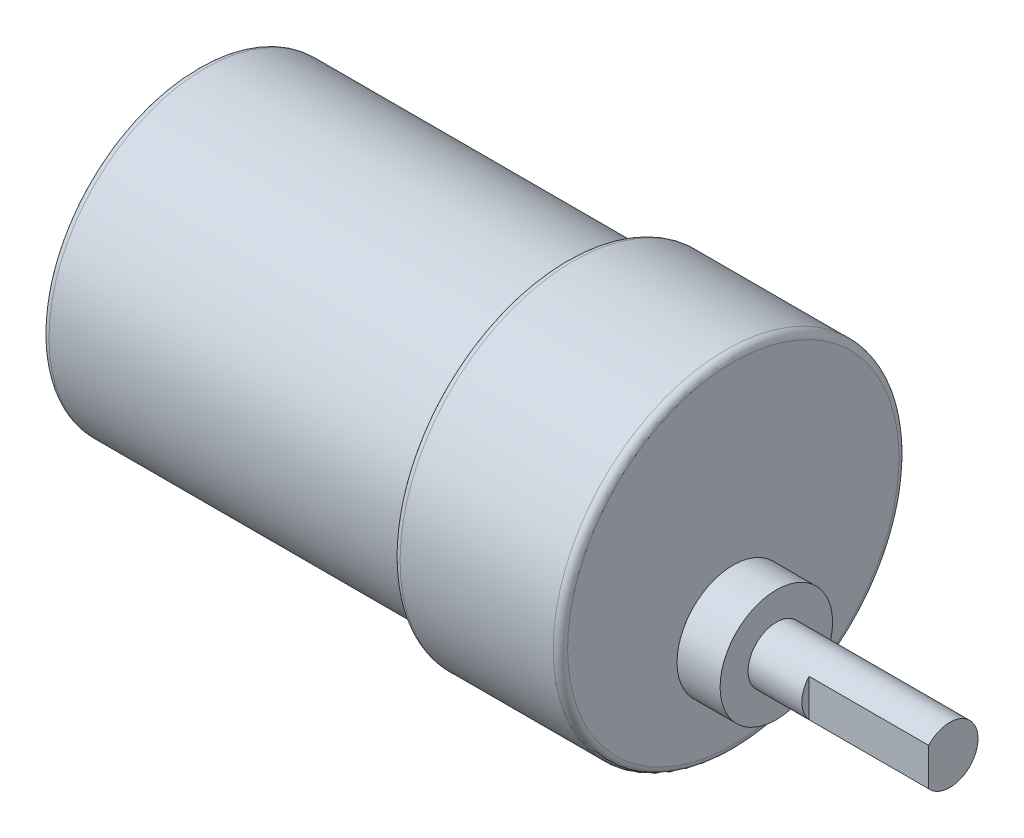
SolidWorks part; units mm, degrees
material "Plain Carbon Steel"
ref_plane "Front Plane" through (0, 0, 0) normal (0, 0, 1) x (1, 0, 0)
ref_plane "Top Plane" through (0, 0, 0) normal (0, 1, 0) x (1, 0, 0)
ref_plane "Right Plane" through (0, 0, 0) normal (1, 0, 0) x (0, 0, -1)
sketch "Sketch1" plane through (0, 0, 0) normal (0, 0, 1) x (1, 0, 0)
  line L0 (0, 3.175) -> (0, 16.51)
  line L1 (0, 16.51) -> (39.116, 16.51)
  line L2 (39.116, 18.3515) -> (56.896, 18.3515)
  line L3 (56.896, 18.3515) -> (56.896, 0)
  line L4 (39.116, 16.51) -> (39.116, 18.3515)
  line L5 (-2.286, 0) -> (56.896, 0) construction
  line L6 (0, 3.175) -> (-2.286, 3.175)
  line L7 (-2.286, 3.175) -> (-2.286, 0)
  line L8 (56.896, 0) -> (-2.286, 0)
  dimension "D1" = 16.51
  dimension "D2" = 39.116
  dimension "D3" = 17.78
  dimension "D4" = 18.3515
  dimension "D5" = 2.286
  dimension "D6" = 3.175
revolve "Revolve1" add sketch "Sketch1" angle 360 about L5
sketch "Sketch2" plane through (56.896, 0, 0) normal (1, 0, 0) x (0, 0, -1)
  line L0 (0, 0) -> (0, -7.0358) construction
  circle A0 centre (0, -7.0358) radius 5.969
  dimension "D2" = 11.938
  dimension "D1" = 7.0358
extrude "Boss-Extrude1" add sketch "Sketch2" along normal blind 4.572
sketch "Sketch3" plane through (61.468, 0, 0) normal (1, 0, 0) x (0, 0, -1)
  circle A0 centre (0, -7.0358) radius 3
  dimension "D1" = 6
extrude "Boss-Extrude2" add sketch "Sketch3" along normal blind 18.415
fillet "Fillet1" radius 0.762 4 edges at (56.896, 0, 18.3515) (39.116, 0, 18.3515) (0, 0, 16.51) (-2.286, 0, 3.175)
sketch "Sketch4" plane through (0, 0, 0) normal (0, 1, 0) x (1, 0, 0)
  line L1 (79.883, -3) -> (67.183, -3)
  line L2 (79.883, -3) -> (79.883, -2.238)
  line L3 (79.883, -2.238) -> (67.183, -2.238)
  line L4 (67.183, -3) -> (67.183, -2.238)
  dimension "D1" = 0.762
  dimension "D2" = 12.7
extrude "Cut-Extrude1" cut sketch "Sketch4" against normal through all
